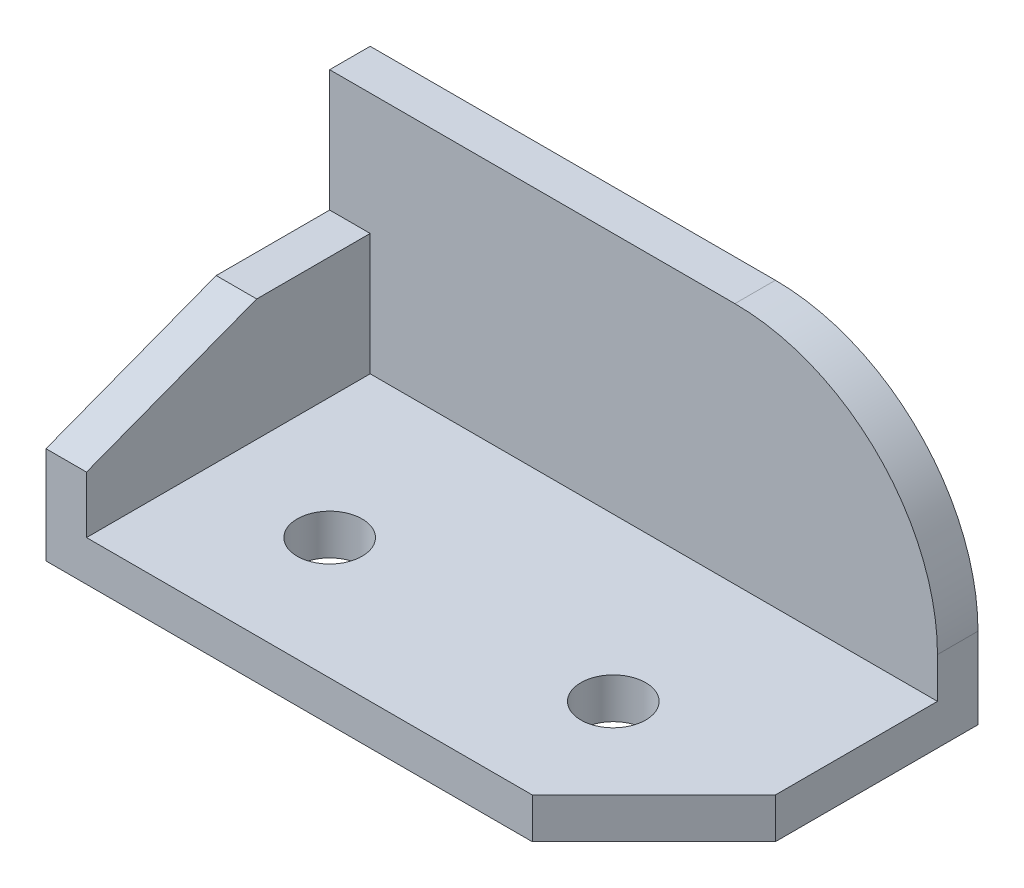
SolidWorks part; units mm, degrees
ref_plane "Front Plane" through (0, 0, 0) normal (0, 0, 1) x (1, 0, 0)
ref_plane "Top Plane" through (0, 0, 0) normal (0, 1, 0) x (1, 0, 0)
ref_plane "Right Plane" through (0, 0, 0) normal (1, 0, 0) x (0, 0, -1)
sketch "Sketch1" plane through (0, 0, 0) normal (0, 1, 0) x (1, 0, 0)
  line L0 (5, -40) -> (5, -5)
  line L1 (0, 0) -> (75, 0)
  line L2 (0, 0) -> (0, -40)
  line L3 (0, -40) -> (60, -40)
  line L4 (75, 0) -> (75, -25)
  line L5 (75, -5) -> (5, -5)
  line L6 (60, -40) -> (75, -25)
  line L7 (5, -5) -> (0, -5)
  circle A0 centre (55, -25) radius 4
  circle A1 centre (20, -25) radius 4
  point P1 (75, -40)
  dimension "D5" = 25
  dimension "D7" = 35
  dimension "D1" = 75
  dimension "D2" = 40
  dimension "D4" = 5
  dimension "D6" = 55
extrude "Boss-Extrude1" add sketch "Sketch1" along normal blind 5 contours L3 L6 L4 L5 L0 A1 A0 region at (38.6036, 0, 21.759)
extrude "Boss-Extrude2" add sketch "Sketch1<3>" along normal blind 35 contours L7 L5 L4 L1 L2 region at (37.5, 0, 2.5)
sketch "Sketch1<3>" plane through (0, 0, 0) normal (0, 1, 0) x (1, 0, 0) same geometry as "Sketch1"
extrude "Boss-Extrude3" add sketch "Sketch1<4>" along normal blind 20 contours L0 L7 L2 L3 region at (2.5, 0, 22.5)
sketch "Sketch1<4>" plane through (0, 0, 0) normal (0, 1, 0) x (1, 0, 0) same geometry as "Sketch1"
chamfer "Chamfer1" distance 8 distance2 21 1 edges at (2.5, 20, 40) first distance on face at (21.6667, 8.3333, 40)
fillet "Fillet1" radius 25 1 edges at (75, 35, 2.5)
